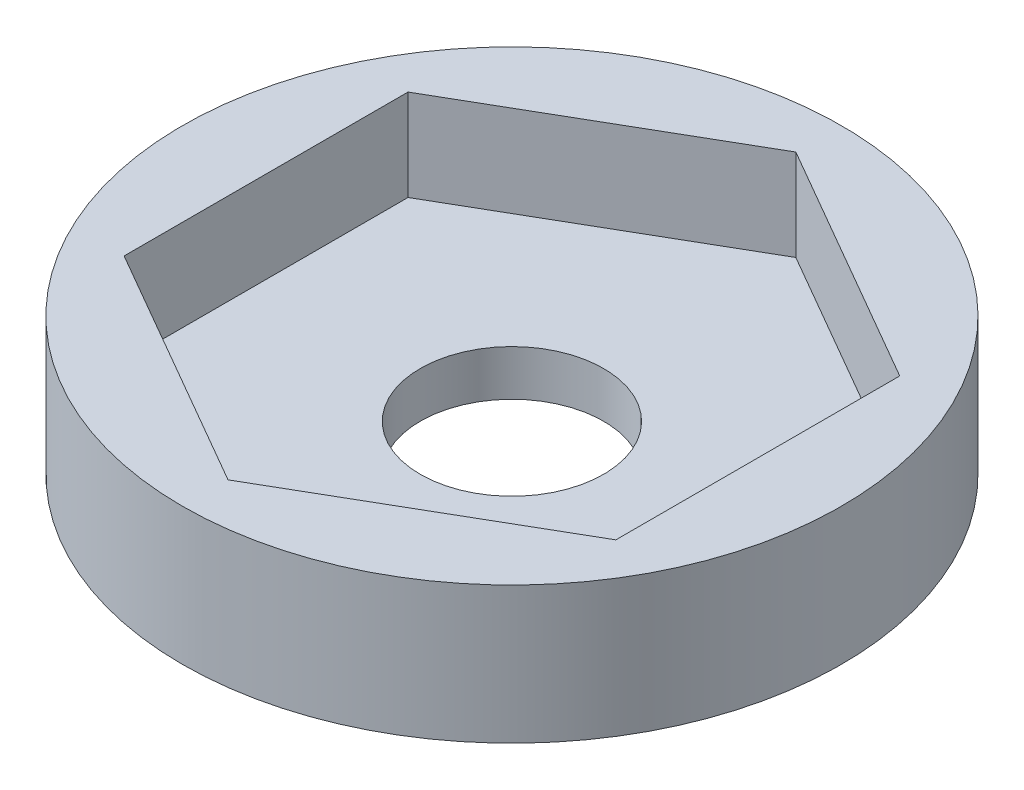
SolidWorks part; units mm, degrees
ref_plane "Front Plane" through (0, 0, 0) normal (0, 0, 1) x (1, 0, 0)
ref_plane "Top Plane" through (0, 0, 0) normal (0, 1, 0) x (1, 0, 0)
ref_plane "Right Plane" through (0, 0, 0) normal (1, 0, 0) x (0, 0, -1)
sketch "Sketch1" plane through (0, 0, 0) normal (0, 1, 0) x (1, 0, 0)
  line L0 (8.5471, -4.9347) -> (9.9219, -5.7284) construction
  line L1 (8.5471, 4.9347) -> (0, 9.8693)
  line L2 (0, 9.8693) -> (-8.5471, 4.9347)
  line L3 (-8.5471, 4.9347) -> (-8.5471, -4.9347)
  line L4 (-8.5471, -4.9347) -> (0, -9.8693)
  line L5 (0, -9.8693) -> (8.5471, -4.9347)
  line L6 (8.5471, -4.9347) -> (8.5471, 4.9347)
  circle A0 centre (0, 0) radius 8.5471 construction
  circle A1 centre (0, 0) radius 11.4568
  dimension "D1" = 17.0942
  dimension "D2" = 1.5875
extrude "Boss-Extrude1" add sketch "Sketch1" along normal blind 3.175
sketch "Sketch2" plane through (0, 0, 0) normal (0, 1, 0) x (1, 0, 0)
  circle A0 centre (0, 0) radius 11.4568
  circle A1 centre (0, 0) radius 3.1877
  circle A2 centre (0, 0) radius 11.4568 construction
  dimension "D1" = 6.3754
extrude "Boss-Extrude2" add sketch "Sketch2" against normal blind 1.5875
sketch "Sketch3" plane through (0, -1.5875, 0) normal (0, -1, 0) x (-1, 0, 0)
  circle A0 centre (0, 0) radius 11.4568
  circle A1 centre (0, 0) radius 11.4568 construction
  circle A2 centre (0, 0) radius 2.794
  dimension "D1" = 5.588
extrude "Boss-Extrude3" [suppressed] add sketch "Sketch3" along normal offset from surface (0.127 mm away) 3.175 from surface
sketch "Sketch4" plane through (0, 0, 0) normal (1, 0, 0) x (0, 0, -1)
  line L0 (11.4568, -1.5875) -> (11.4568, 0)
  line L1 (11.4568, -1.5875) -> (11.4568, 3.175) construction
  line L2 (11.4568, -1.5875) -> (5.569, -1.5875)
  line L3 (-11.4568, -1.5875) -> (11.4568, -1.5875) construction
  line L4 (5.569, -1.5875) -> (5.569, 0.9525)
  line L5 (5.569, 0.9525) -> (11.1494, -0.2483)
  line L6 (11.4568, -1.5875) -> (11.4568, 3.175) construction
  line L7 (4.9347, 0) -> (9.8693, 0) construction
  line L8 (3.1877, -1.5875) -> (3.1877, 0) construction
  line L9 (0, 0) -> (0, -1.5875) construction
  arc A0 (11.4568, 0) -> (11.1494, -0.2483) centre (11.2028, 0) cw
  dimension "D3" = 0.254
  dimension "D1" = 2.54
  dimension "D2" = 2.3813
revolve "Cut-Revolve1" [suppressed] cut sketch "Sketch4" angle 360 about L9
fillet "Fillet1" [suppressed] radius 2.54
